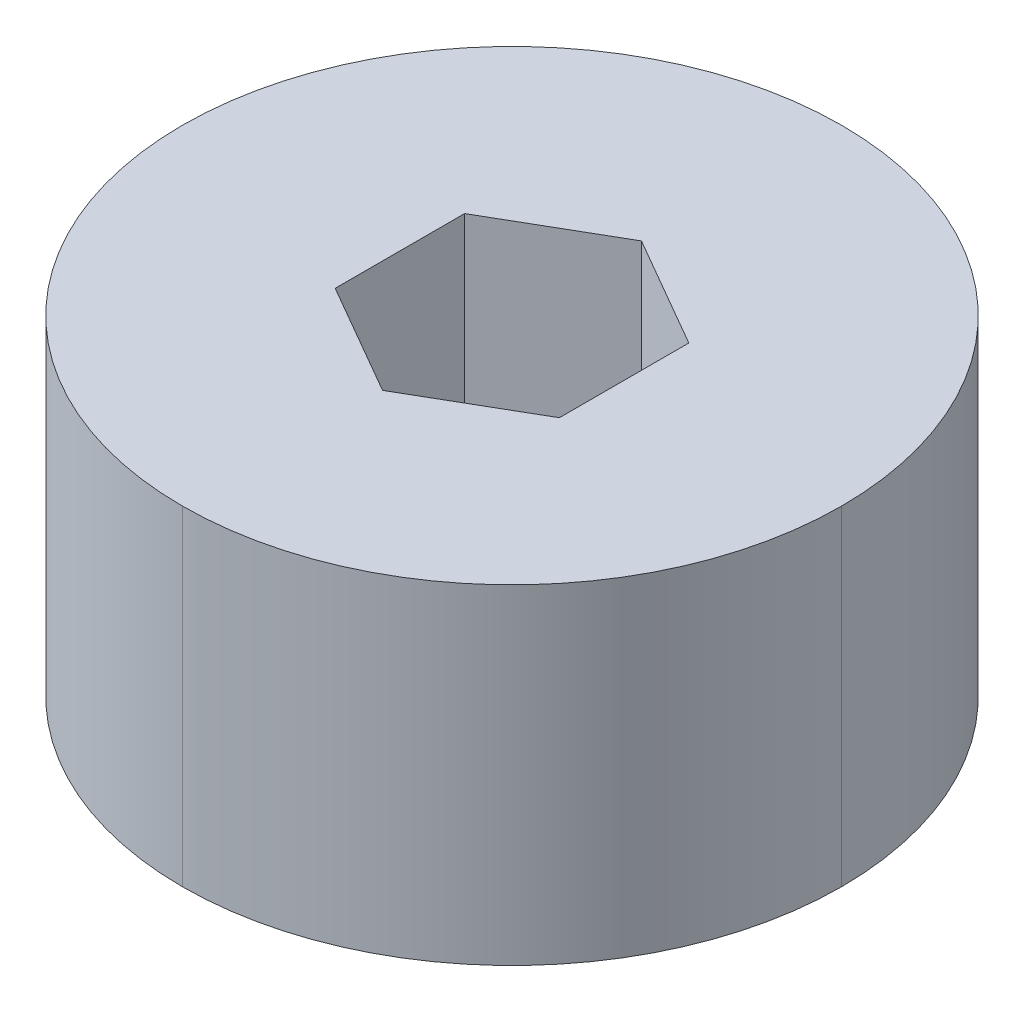
SolidWorks part; units mm, degrees
ref_plane "Front Plane" through (0, 0, 0) normal (0, 0, 1) x (1, 0, 0)
ref_plane "Top Plane" through (0, 0, 0) normal (0, 1, 0) x (1, 0, 0)
ref_plane "Right Plane" through (0, 0, 0) normal (1, 0, 0) x (0, 0, -1)
sketch "Sketch1" plane through (0, 0, 0) normal (0, 1, 0) x (1, 0, 0)
  line L1 (-10, -10) -> (10, -10)
  line L2 (-10, -10) -> (-10, 10)
  line L3 (-10, 10) -> (10, 10)
  line L4 (10, -10) -> (10, 10)
  line L5 (-10, -10) -> (10, 10) construction
  line L6 (-10, 10) -> (10, -10) construction
  point P0 (0, 0)
  dimension "D1" = 20
extrude "Boss-Extrude1" add sketch "Sketch1" along normal blind 10
sketch "Sketch2" plane through (0, 10, 0) normal (0, 1, 0) x (1, 0, 0)
  line L1 (0, 3.926) -> (-3.4, 1.963)
  line L2 (-3.4, 1.963) -> (-3.4, -1.963)
  line L3 (-3.4, -1.963) -> (0, -3.926)
  line L4 (0, -3.926) -> (3.4, -1.963)
  line L5 (3.4, -1.963) -> (3.4, 1.963)
  line L6 (3.4, 1.963) -> (0, 3.926)
  circle A0 centre (0, 0) radius 3.4 construction
  dimension "D1" = 6.8
extrude "Cut-Extrude1" cut sketch "Sketch2" against normal blind 5
fillet "Fillet1" radius 10 4 edges at (10, 5, -10) (10, 5, 10) (-10, 5, -10) (-10, 5, 10)
